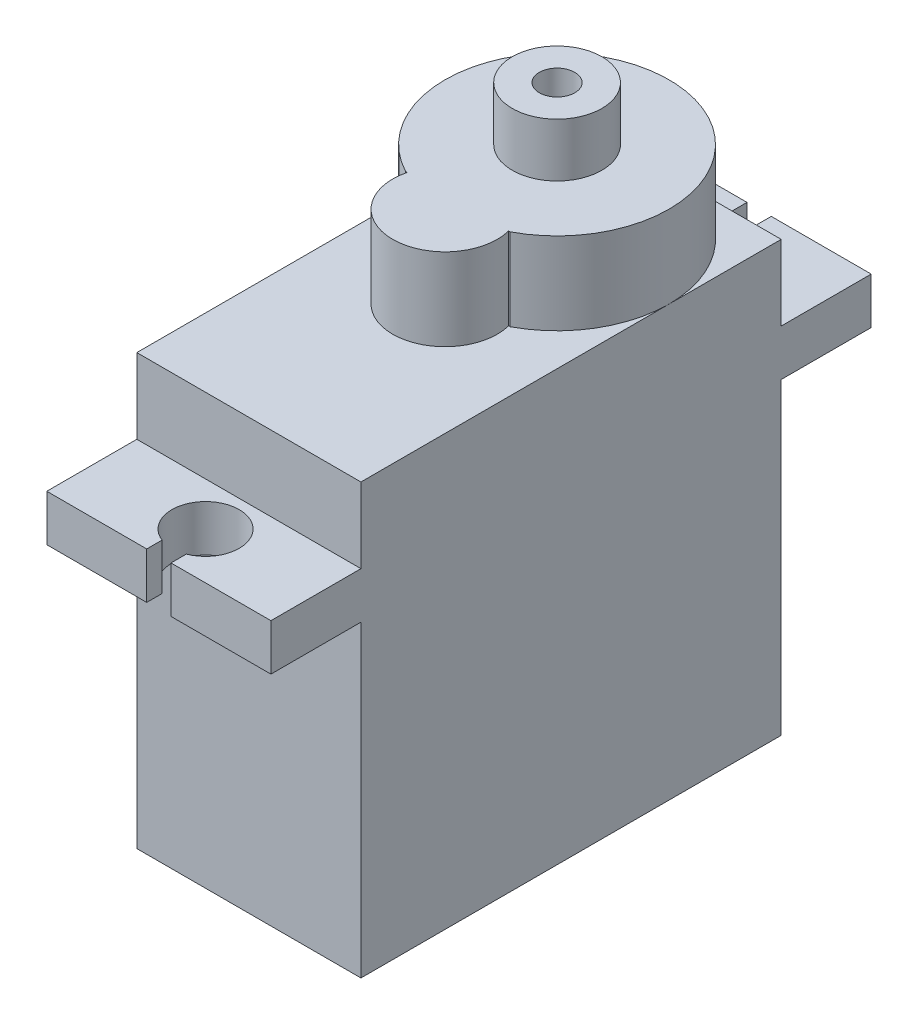
SolidWorks part; units mm, degrees
ref_plane "Front Plane" through (0, 0, 0) normal (0, 0, 1) x (1, 0, 0)
ref_plane "Top Plane" through (0, 0, 0) normal (0, 1, 0) x (1, 0, 0)
ref_plane "Right Plane" through (0, 0, 0) normal (1, 0, 0) x (0, 0, -1)
sketch "Sketch2" plane through (0, 0, 0) normal (1, 0, 0) x (0, 0, -1)
  line L5 (-11.25, 11.5) -> (11.25, 11.5)
  line L6 (-11.25, 11.5) -> (-11.25, -11.5)
  line L15 (-11.25, -11.5) -> (11.25, -11.5)
  line L16 (11.25, 11.5) -> (11.25, -11.5)
  line L17 (-11.25, 11.5) -> (11.25, -11.5) construction
  line L18 (-11.25, -11.5) -> (11.25, 11.5) construction
  point P0 (0, 0)
  dimension "D1" = 23
  dimension "D2" = 22.5
extrude "Boss-Extrude1" add sketch "Sketch2" along normal blind 12
sketch "Sketch19" plane through (0, 0, 11.25) normal (0, 0, 1) x (1, 0, 0)
  line L0 (12, 11.5) -> (12, -11.5) construction
  line L1 (0, 5) -> (12, 5)
  line L2 (0, 5) -> (0, -11.5)
  line L3 (0, -11.5) -> (12, -11.5)
  line L4 (12, 5) -> (12, -11.5)
  line L5 (0, 5) -> (12, -11.5) construction
  line L6 (0, -11.5) -> (12, 5) construction
  line L7 (12, -11.5) -> (0, -11.5) construction
  line L8 (0, 11.5) -> (0, -11.5) construction
  line L10 (0, 7.48) -> (12, 7.48)
  line L11 (0, 7.48) -> (0, 5)
  line L12 (0, 5) -> (12, 5)
  line L13 (12, 7.48) -> (12, 5)
  line L14 (0, 7.48) -> (12, 5) construction
  line L15 (0, 5) -> (12, 7.48) construction
  point P0 (6, -3.25)
  point P11 (6, 6.24)
  line M8 (0, 11.5) -> (0, -11.5)
  line M10 (12, -11.5) -> (12, 11.5)
  dimension "D1" = 2.48
  dimension "D2" = 16.5
extrude "Boss-Extrude8" add sketch "Sketch19" along normal blind 4.82 contours L10 L1 M8 M10 region at (6, 6.24, 11.25)
sketch "Sketch20" plane through (0, 0, -11.25) normal (0, 0, -1) x (-1, 0, 0)
  line L0 (-12, -11.5) -> (0, -11.5) construction
  line L1 (-12, 5) -> (0, 5)
  line L2 (-12, 5) -> (-12, -11.5)
  line L3 (-12, -11.5) -> (0, -11.5)
  line L4 (0, 5) -> (0, -11.5)
  line L5 (-12, 5) -> (0, -11.5) construction
  line L6 (-12, -11.5) -> (0, 5) construction
  line L8 (-12, -11.5) -> (-12, 11.5) construction
  line L9 (0, -11.5) -> (0, 11.5) construction
  line L11 (-12, 7.48) -> (0, 7.48)
  line L12 (-12, 7.48) -> (-12, 5)
  line L13 (-12, 5) -> (0, 5)
  line L14 (0, 7.48) -> (0, 5)
  line L15 (-12, 7.48) -> (0, 5) construction
  line L16 (-12, 5) -> (0, 7.48) construction
  point P0 (-6, -3.25)
  point P11 (-6, 6.24)
  line M8 (0, -11.5) -> (0, 11.5)
  line M10 (-12, 11.5) -> (-12, -11.5)
  dimension "D1" = 2.48
  dimension "D2" = 16.5
extrude "Boss-Extrude9" add sketch "Sketch20" along normal blind 4.82 contours L11 L1 M10 M8 region at (6, 6.24, -11.25)
sketch "Sketch21" plane through (0, 11.5, 0) normal (0, 1, 0) x (1, 0, 0)
  line L0 (12, 11.25) -> (12, -11.25) construction
  line L1 (0, -3.55) -> (12, -3.55)
  line L2 (0, -3.55) -> (0, -11.25)
  line L3 (0, -11.25) -> (12, -11.25)
  line L4 (12, -3.55) -> (12, -11.25)
  line L5 (0, -3.55) -> (12, -11.25) construction
  line L6 (0, -11.25) -> (12, -3.55) construction
  line L7 (0, -11.25) -> (12, -11.25) construction
  line L8 (0, 11.25) -> (0, -11.25) construction
  line L9 (12, 11.25) -> (0, 11.25) construction
  line L10 (6, 11.25) -> (6, -11.25) construction
  line L18 (3.2, -0.0566) -> (8.8, -0.0566)
  line L19 (3.2, -0.0566) -> (3.2, -0.75)
  line L20 (3.2, -0.75) -> (8.8, -0.75)
  line L21 (8.8, -0.0566) -> (8.8, -0.75)
  line L22 (3.2, -0.0566) -> (8.8, -0.75) construction
  line L23 (3.2, -0.75) -> (8.8, -0.0566) construction
  line L24 (0, -0.75) -> (12, -0.75)
  line L25 (0, -0.75) -> (0, -3.55)
  line L26 (0, -3.55) -> (12, -3.55)
  line L27 (12, -0.75) -> (12, -3.55)
  line L28 (0, -0.75) -> (12, -3.55) construction
  line L29 (0, -3.55) -> (12, -0.75) construction
  circle A0 centre (6, 5.25) radius 6
  circle A1 centre (6, -0.75) radius 2.8
  circle A2 centre (6, 5.25) radius 2.4
  circle A3 centre (6, 5.25) radius 0.95
  point P0 (6, -7.4)
  point P12 (6, -2.15)
  point P16 (6, -0.4033)
  point P23 (6, 30.6017)
  dimension "D1" = 2.8
  dimension "D2" = 4.8
  dimension "D3" = 1.9
  dimension "D4" = 7.7
extrude "Boss-Extrude10" add sketch "Sketch21" along normal blind 4.4 from surface contours A1 A0 A2 | L24 A1 A0 | A0 A1 L20 | A1 L24 L20 | L18 A1 | A0 A1 L18 | A1 region at (6, 11.5, 1.9384) region at (3.9116, 11.5, 0.5531) region at (8.0884, 11.5, 0.5531) region at (2.9868, 11.5, -10.2469) region at (6, 11.5, 0.3357) region at (6, 11.5, -0.821) starting at face at (6, 11.5, 0)
extrude "Boss-Extrude11" add sketch "Sketch21<3>" along normal blind 7.27 from surface contours A2 A3 region at (3.6679, 11.5, -5.25) starting at face at (6, 11.5, -7.65)
sketch "Sketch21<3>" plane through (0, 11.5, 0) normal (0, 1, 0) x (1, 0, 0) same geometry as "Sketch21"
sketch "Sketch23" plane through (0, 7.48, 0) normal (0, 1, 0) x (1, 0, 0)
  line L0 (5.35, -16.07) -> (6.65, -16.07)
  line L5 (6, 16.07) -> (6, -16.07) construction
  line L6 (12, 16.07) -> (0, 16.07) construction
  line L8 (9.4681, 11.25) -> (9, 11.25) construction
  line L9 (12, 11.25) -> (6, 11.25) construction
  line L10 (0, -16.07) -> (12, -16.07)
  line L11 (0, -16.07) -> (0, -13.57)
  line L12 (0, -13.57) -> (4.2, -13.57)
  line L13 (12, -16.07) -> (12, -13.57)
  line L14 (9, 11.25) -> (9, -11.25) construction
  line L15 (0, -11.25) -> (12, -11.25) construction
  line L16 (9, 0) -> (0, 0) construction
  line L17 (0, -16.07) -> (12, -16.07) construction
  line L18 (0, -16.07) -> (0, -11.25) construction
  line L19 (12, -16.07) -> (12, -11.25) construction
  line L20 (7.8, -13.57) -> (12, -13.57)
  line L26 (0, 5.25) -> (0, -11.25) construction
  line L29 (5.35, -15.2485) -> (5.35, -16.07)
  line L31 (6.65, -15.2485) -> (6.65, -16.07)
  line L32 (0, 0) -> (12, 0) construction
  line L33 (12, 5.25) -> (12, -11.25) construction
  arc A1 (6.65, -15.2485) -> (5.35, -15.2485) centre (6, -13.57) ccw
  point P14 (6, 11.2467)
  point P33 (6, 11.2467)
  dimension "D1" = 4.2
  dimension "D6" = 1.8
  dimension "D2" = 4.2
  dimension "D3" = 1.3
  dimension "D7" = 0.8215
  dimension "D10" = 2.5
extrude "Cut-Extrude5" cut sketch "Sketch23" against normal blind 2.49 from surface contours L31 A1 L29 L0 region at (6, 7.48, 13.7538) starting at face at (6, 7.48, 13.66)
mirror "Mirror3" about plane through (0, 0, 0) normal (0, 0, 1) of "Cut-Extrude5"
